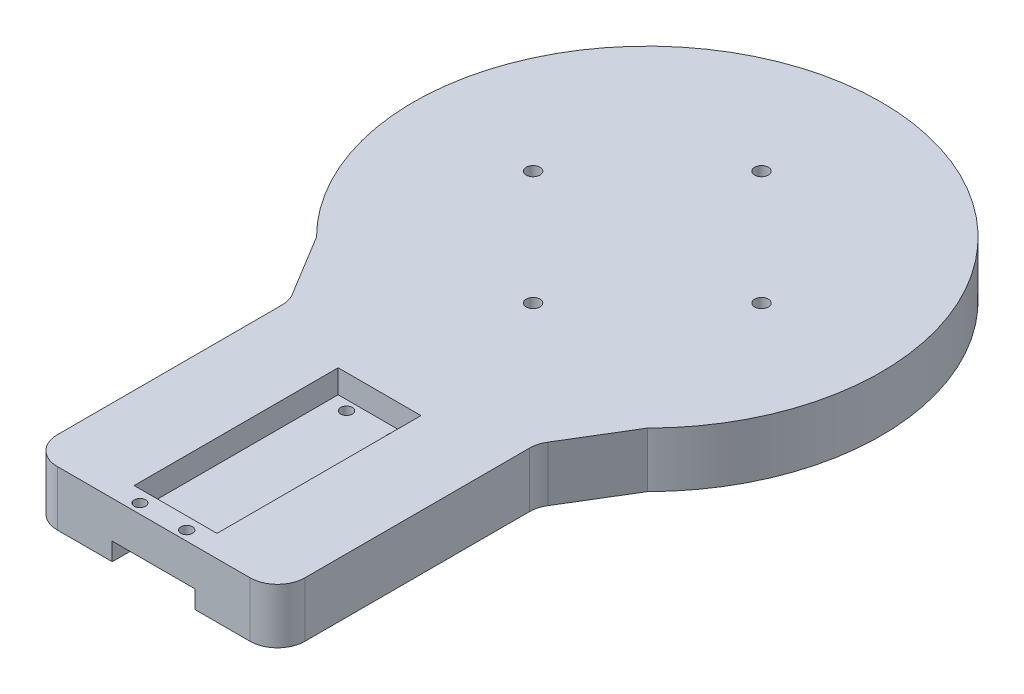
SolidWorks part; units mm, degrees
ref_plane "Front Plane" through (0, 0, 0) normal (0, 0, 1) x (1, 0, 0)
ref_plane "Top Plane" through (0, 0, 0) normal (0, 1, 0) x (1, 0, 0)
ref_plane "Right Plane" through (0, 0, 0) normal (1, 0, 0) x (0, 0, -1)
sketch "Sketch1" plane through (0, 0, 0) normal (0, 1, 0) x (1, 0, 0)
  line L0 (0, 85) -> (0, -179.39) construction
  line L1 (-85, 85) -> (85, 85) construction
  line L2 (-85, 85) -> (-85, -85) construction
  line L3 (-85, -85) -> (-45, -85) construction
  line L4 (85, 85) -> (85, -85) construction
  line L5 (-85, 85) -> (85, -85) construction
  line L6 (-85, -85) -> (85, 85) construction
  line L7 (-85, 0) -> (85, 0) construction
  line L8 (0, -47.195) -> (0, -179.39) construction
  line L9 (-45, -85) -> (-45, -179.39) construction
  line L10 (-45, -179.39) -> (45, -179.39) construction
  line L11 (45, -179.39) -> (45, -85) construction
  line L12 (45, -85) -> (85, -85) construction
  line L13 (60.1041, -60.1041) -> (46.4504, -82.6093)
  line L14 (-60.1041, -60.1041) -> (-46.4504, -82.6093)
  line L15 (-45, -87.7963) -> (-45, -118.89)
  line L16 (45, -87.7963) -> (45, -118.89)
  line L17 (-45, -118.89) -> (-45, -169.39)
  line L18 (-35, -179.39) -> (35, -179.39)
  line L19 (45, -169.39) -> (45, -118.89)
  circle A0 centre (0, 41.5) radius 2.5
  circle A1 centre (41.5, 0) radius 2.5
  circle A2 centre (0, -41.5) radius 2.5
  circle A3 centre (-41.5, 0) radius 2.5
  arc A4 (60.1041, -60.1041) -> (-60.1041, -60.1041) centre (0, 0) ccw
  arc A7 (35, -179.39) -> (45, -169.39) centre (35, -169.39) ccw
  arc A8 (-45, -169.39) -> (-35, -179.39) centre (-35, -169.39) ccw
  arc A9 (-45, -87.7963) -> (-46.4504, -82.6093) centre (-55, -87.7963) ccw
  arc A10 (45, -87.7963) -> (46.4504, -82.6093) centre (55, -87.7963) cw
  point P0 (0, 0)
  point P21 (0, 0)
  point P23 (0, -179.39)
  point P26 (0, -118.89)
  point P30 (60.1041, -60.1041)
  point P31 (-60.1041, -60.1041)
  point P32 (45, -118.89)
  point P33 (-45, -118.89)
  dimension "D3" = 5
  dimension "D8" = 170
  dimension "D10" = 10
  dimension "D11" = 10
  dimension "D1" = 170
  dimension "D2" = 170
  dimension "D4" = 41.5
  dimension "D6" = 179.39
  dimension "D7" = 90
  dimension "D9" = 60.5
  dimension "D5" = 4
extrude "Boss-Extrude1" add sketch "Sketch1" along normal blind 20
sketch "Sketch2" plane through (0, 20, 0) normal (0, 1, 0) x (1, 0, 0)
  line L0 (-35, -179.39) -> (35, -179.39) construction
  line L1 (-15.05, -97.29) -> (15.05, -97.29)
  line L2 (-15.05, -97.29) -> (-15.05, -179.39)
  line L3 (-15.05, -179.39) -> (15.05, -179.39)
  line L4 (15.05, -97.29) -> (15.05, -179.39)
  line L5 (-15.05, -97.29) -> (15.05, -179.39) construction
  line L6 (-15.05, -179.39) -> (15.05, -97.29) construction
  point P0 (0, -138.34)
  point P7 (0, -179.39)
  dimension "D1" = 82.1
  dimension "D2" = 30.1
extrude "Cut-Extrude1" cut sketch "Sketch2" against normal blind 8.5
sketch "Sketch3" plane through (0, 0, 0) normal (0, -1, 0) x (1, 0, 0)
  line L4 (-15.05, 97.29) -> (15.05, 97.29)
  line L5 (15.05, 97.29) -> (15.05, 179.39)
  line L6 (15.05, 179.39) -> (-15.05, 179.39)
  line L7 (-15.05, 179.39) -> (-15.05, 97.29)
  line L8 (-15.05, 97.29) -> (15.05, 97.29)
  line L9 (15.05, 97.29) -> (15.05, 179.39)
  line L10 (15.05, 179.39) -> (-15.05, 179.39)
  line L11 (-15.05, 179.39) -> (-15.05, 97.29)
  dimension "D1" = 0
extrude "Cut-Extrude2" cut sketch "Sketch3" against normal blind 6.5
sketch "Sketch5" plane through (0, 11.5, 0) normal (0, 1, 0) x (1, 0, 0)
  line L0 (-15.05, -179.39) -> (15.05, -179.39) construction
  line L1 (15.05, -179.39) -> (15.05, -97.29) construction
  line L2 (-15.05, -97.29) -> (-15.05, -179.39) construction
  line L3 (15.05, -97.29) -> (-15.05, -97.29) construction
  line L4 (-15.05, -179.39) -> (15.05, -179.39) construction
  line L5 (15.05, -179.39) -> (15.05, -97.29) construction
  line L6 (-15.05, -97.29) -> (-15.05, -179.39) construction
  line L7 (15.05, -97.29) -> (-15.05, -97.29) construction
  line L8 (0, -97.29) -> (0, -179.39) construction
  line L9 (-15.05, -138.34) -> (15.05, -138.34) construction
  circle A0 centre (-8.5, -100.8) radius 2.1
  circle A1 centre (8.5, -100.8) radius 2.1
  circle A2 centre (8.5, -175.88) radius 2.1
  circle A3 centre (-8.5, -175.88) radius 2.1
  dimension "D3" = 4.2
  dimension "D1" = 8.5
  dimension "D2" = 3.51
  dimension "D4" = 17
extrude "Cut-Extrude3" cut sketch "Sketch5" against normal up to next
sketch "Sketch6" plane through (0, 11.5, 0) normal (0, 1, 0) x (1, 0, 0)
  line L0 (15.05, -179.39) -> (-15.05, -179.39)
  line L1 (-15.05, -179.39) -> (-15.05, -171.4204)
  line L2 (-15.05, -97.29) -> (-15.05, -179.39) construction
  line L3 (-15.05, -171.4204) -> (15.05, -171.4204)
  line L4 (15.05, -179.39) -> (15.05, -97.29) construction
  line L5 (15.05, -171.4204) -> (15.05, -179.39)
  circle A0 centre (8.5, -175.88) radius 2.1
  circle A1 centre (-8.5, -175.88) radius 2.0566
extrude "Boss-Extrude2" add sketch "Sketch6" along normal blind 8.5
